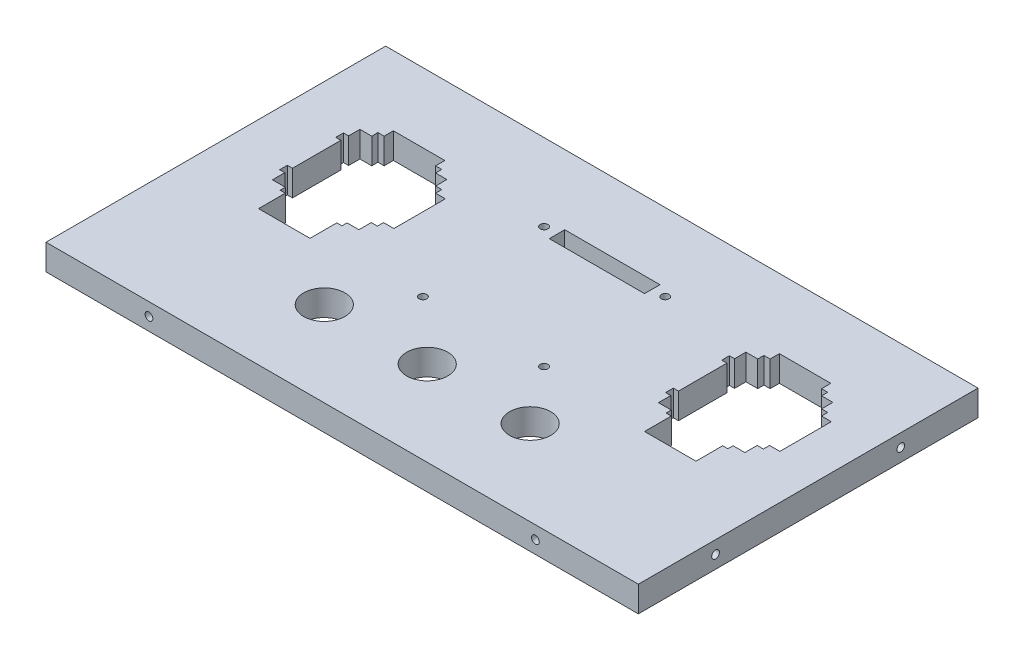
SolidWorks part; units mm, degrees
ref_plane "前视基准面" through (0, 0, 0) normal (0, 0, 1) x (1, 0, 0)
ref_plane "上视基准面" through (0, 0, 0) normal (0, 1, 0) x (1, 0, 0)
ref_plane "右视基准面" through (0, 0, 0) normal (1, 0, 0) x (0, 0, -1)
other "Configuration Table"
sketch "草图1" plane through (0, 0, 0) normal (0, 1, 0) x (1, 0, 0)
  line L1 (0, 0) -> (115.1, 0)
  line L2 (0, 0) -> (0, -66)
  line L3 (0, -66) -> (115.1, -66)
  line L4 (115.1, 0) -> (115.1, -66)
  line L9 (48.3, -13.5) -> (66.8, -13.5)
  line L10 (11.5, -18.7) -> (10.5, -18.7)
  line L11 (31.5, -33.5) -> (11.5, -33.5)
  line L12 (31.5, -33.5) -> (31.5, -13.5)
  line L13 (31.5, -13.5) -> (11.5, -13.5)
  line L14 (11.5, -33.5) -> (11.5, -13.5)
  line L15 (11.5, -18.7) -> (11.5, -20.2)
  line L16 (11.5, -20.2) -> (10.5, -20.2)
  line L17 (10.5, -18.7) -> (10.5, -20.2)
  line L22 (11.5, -29.6) -> (10.5, -29.6)
  line L23 (11.5, -29.6) -> (11.5, -31.1)
  line L24 (11.5, -31.1) -> (10.5, -31.1)
  line L25 (10.5, -29.6) -> (10.5, -31.1)
  line L26 (15, -33.5) -> (25, -33.5)
  line L27 (15, -33.5) -> (15, -39.7)
  line L28 (15, -39.7) -> (25, -39.7)
  line L29 (25, -33.5) -> (25, -39.7)
  line L30 (14, -33.5) -> (15, -33.5)
  line L31 (14, -33.5) -> (14, -34.5)
  line L32 (14, -34.5) -> (15, -34.5)
  line L33 (15, -33.5) -> (15, -34.5)
  line L34 (25, -34.5) -> (26, -34.5)
  line L35 (25, -34.5) -> (25, -33.5)
  line L36 (25, -33.5) -> (26, -33.5)
  line L37 (26, -34.5) -> (26, -33.5)
  line L38 (11.5, -13.5) -> (15, -13.5)
  line L39 (11.5, -13.5) -> (11.5, -16.5)
  line L40 (11.5, -16.5) -> (15, -16.5)
  line L41 (15, -13.5) -> (15, -16.5)
  line L42 (13.8, -15.3) -> (15, -15.3)
  line L43 (13.8, -15.3) -> (13.8, -16.5)
  line L44 (13.8, -16.5) -> (15, -16.5)
  line L45 (15, -15.3) -> (15, -16.5)
  line L46 (31.5, -13.5) -> (25, -13.5)
  line L47 (31.5, -13.5) -> (31.5, -19.9)
  line L48 (31.5, -19.9) -> (25, -19.9)
  line L49 (25, -13.5) -> (25, -19.9)
  line L50 (25, -19.9) -> (28.4, -19.9)
  line L51 (25, -19.9) -> (25, -16.5)
  line L52 (25, -16.5) -> (28.4, -16.5)
  line L53 (28.4, -19.9) -> (28.4, -16.5)
  line L54 (25, -16.5) -> (26.2, -16.5)
  line L55 (25, -16.5) -> (25, -15.3)
  line L56 (25, -15.3) -> (26.2, -15.3)
  line L57 (26.2, -16.5) -> (26.2, -15.3)
  line L58 (28.4, -19.9) -> (29.6, -19.9)
  line L59 (28.4, -19.9) -> (28.4, -18.7)
  line L60 (28.4, -18.7) -> (29.6, -18.7)
  line L61 (29.6, -19.9) -> (29.6, -18.7)
  line L62 (31.5, -33.5) -> (28.3, -33.5)
  line L63 (31.5, -33.5) -> (31.5, -29.9)
  line L64 (31.5, -29.9) -> (28.3, -29.9)
  line L65 (28.3, -33.5) -> (28.3, -29.9)
  line L66 (28.3, -29.9) -> (29.5, -29.9)
  line L67 (28.3, -29.9) -> (28.3, -31.1)
  line L68 (28.3, -31.1) -> (29.5, -31.1)
  line L69 (29.5, -29.9) -> (29.5, -31.1)
  line L70 (48.3, -13.5) -> (48.3, -16.5)
  line L71 (48.3, -16.5) -> (66.8, -16.5)
  line L72 (66.8, -13.5) -> (66.8, -16.5)
  circle A2 centre (45.78, -15) radius 0.75
  circle A3 centre (69.32, -15) radius 0.75
  circle A4 centre (45.78, -38.545) radius 0.75
  circle A5 centre (69.32, -38.545) radius 0.75
  point P11 (57.55, -13.5)
  point P12 (57.55, 0)
  dimension "D28" = 1.5
  dimension "D29" = 66
  dimension "D1" = 115.1
  dimension "D3" = 3
  dimension "D4" = 13.5
  dimension "D5" = 11.5
  dimension "D6" = 31.5
  dimension "D7" = 20
  dimension "D8" = 1
  dimension "D9" = 1.5
  dimension "D10" = 5.2
  dimension "D11" = 9.4
  dimension "D12" = 6.2
  dimension "D13" = 3.5
  dimension "D14" = 10
  dimension "D15" = 1
  dimension "D16" = 3
  dimension "D17" = 3.5
  dimension "D18" = 1.2
  dimension "D19" = 6.5
  dimension "D20" = 6.4
  dimension "D21" = 3.4
  dimension "D22" = 3.4
  dimension "D23" = 1.2
  dimension "D24" = 3.6
  dimension "D25" = 3.2
  dimension "D26" = 1.2
  dimension "D27" = 18.5
extrude "凸台-拉伸1" add sketch "草图1" along normal blind 5 contours L2 L3 L4 L1
extrude "切除-拉伸1" cut sketch "草图1<3>" along normal through all contours L29 L11 L27 L28 | L34 L37 L11 L29 | L31 L32 L27 L11 | L11 L65 L64 L12 L48 L49 L13 L41 L40 L14 | L22 L25 L24 L14 | L10 L17 L16 L14 | L52 L57 L56 L49 | L48 L53 L52 L49 | L48 L61 L60 L53 | L69 L64 L65 L68 | L44 L43 L42 L45 region at (11, 0, 19.45) region at (20.6351, 0, 24.3255) region at (11, 0, 30.35) region at (14.5, 0, 34) region at (25.6, 0, 15.9) region at (20, 0, 36.6) region at (26.7, 0, 18.2) region at (25.5, 0, 34) region at (29, 0, 19.3) region at (28.9, 0, 30.5)
sketch "草图1<3>" plane through (0, 0, 0) normal (0, 1, 0) x (1, 0, 0) same geometry as "草图1"
ref_plane "基准面1" through (60, 0, 0) normal (-1, 0, 0) x (0, 0, 1)
pattern_linear "阵列(线性)1" count 2 spacing 75 along (1, 0, 0) of "切除-拉伸1"
extrude "切除-拉伸2" cut sketch "草图1<4>" along normal through all contours L71 L72 L9 L70 | A3 | A5 | A4 | A2
sketch "草图1<4>" plane through (0, 0, 0) normal (0, 1, 0) x (1, 0, 0) same geometry as "草图1"
sketch "草图2" plane through (0, 5, 0) normal (0, 1, 0) x (1, 0, 0)
  circle A0 centre (37.55, -49.4744) radius 4
  circle A1 centre (57.55, -49.4744) radius 4
  circle A2 centre (77.55, -49.4744) radius 4
  dimension "D1" = 8
extrude "切除-拉伸3" cut sketch "草图2" against normal through all contours A0 | A1 | A2
sketch "草图5" plane through (0, 0, 0) normal (0, -1, 0) x (1, 0, 0)
  circle A0 centre (104.5, 35.5) radius 0.75
  circle A1 centre (86.5, 13.5) radius 0.75
  circle A2 centre (104.5, 13.5) radius 0.75
  circle A3 centre (86.5, 35.5) radius 0.75
  circle A4 centre (11.5, 35.5) radius 0.75
  circle A5 centre (11.5, 13.5) radius 0.75
  circle A6 centre (29.5, 13.5) radius 0.75
  circle A7 centre (29.5, 35.5) radius 0.75
  circle A8 centre (47.05, 48.9244) radius 0.75
  circle A9 centre (68.05, 48.9244) radius 0.75
  dimension "D1" = 1.5
  dimension "D2" = 1.5
extrude "切除-拉伸4" cut sketch "草图5" against normal blind 3
sketch "草图6" plane through (0, 0, 0) normal (-1, 0, 0) x (0, 0, 1)
  line L0 (0, 5) -> (66, 5) construction
  line L1 (0, 5) -> (0, 0) construction
  line L2 (66, 5) -> (66, 0) construction
  circle A0 centre (15, 2.5) radius 0.75
  circle A1 centre (51, 2.5) radius 0.75
  dimension "D1" = 1.5
  dimension "D2" = 2.5
  dimension "D3" = 15
  dimension "D4" = 15
extrude "切除-拉伸5" cut sketch "草图6" against normal blind 4 contours A0 | A1
extrude "切除-拉伸6" cut sketch "草图6<4>" along normal blind 4 from surface starting at face at (115.1, 2.5, 33)
sketch "草图6<4>" plane through (0, 0, 0) normal (-1, 0, 0) x (0, 0, 1) same geometry as "草图6"
sketch "草图7" plane through (0, 0, 66) normal (0, 0, 1) x (1, 0, 0)
  line L0 (0, 5) -> (115.1, 5) construction
  line L1 (0, 5) -> (0, 0) construction
  line L2 (115.1, 5) -> (115.1, 0) construction
  circle A0 centre (95.1, 2.5) radius 0.75
  circle A1 centre (20, 2.5) radius 0.75
  dimension "D1" = 1.5
  dimension "D2" = 2.5
  dimension "D3" = 20
  dimension "D4" = 20
extrude "切除-拉伸7" cut sketch "草图7" against normal blind 4
extrude "切除-拉伸8" cut sketch "草图7<2>" along normal blind 4 from surface starting at face at (57.55, 2.5, 0)
sketch "草图7<2>" plane through (0, 0, 66) normal (0, 0, 1) x (1, 0, 0) same geometry as "草图7"
